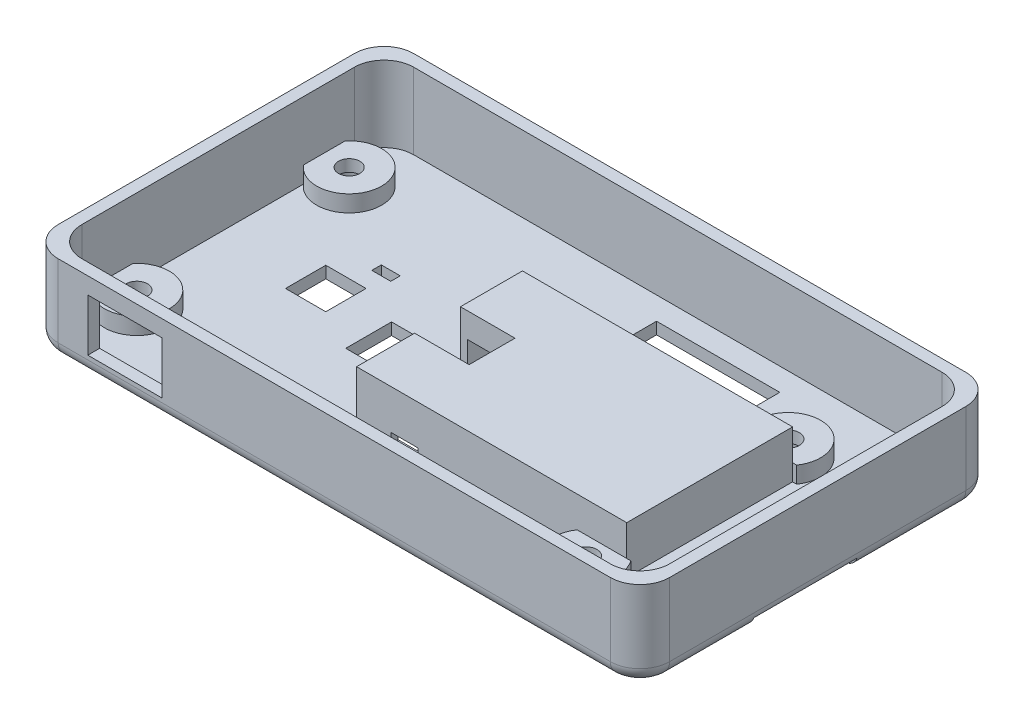
SolidWorks part; units mm, degrees
material "ABS"
ref_plane "Спереди" through (0, 0, 0) normal (0, 0, 1) x (1, 0, 0)
ref_plane "Сверху" through (0, 0, 0) normal (0, 1, 0) x (1, 0, 0)
ref_plane "Справа" through (0, 0, 0) normal (1, 0, 0) x (0, 0, -1)
sketch "Эскиз1" plane through (0, 0, 0) normal (0, 1, 0) x (1, 0, 0)
  line L11 (61.92, -36) -> (-61.92, -36)
  line L12 (61.92, -36) -> (61.92, 36)
  line L13 (61.92, 36) -> (-61.92, 36)
  line L14 (-61.92, -36) -> (-61.92, 36)
  point P0 (0, 0)
extrude "Бобышка-Вытянуть1" add sketch "Эскиз1" along normal blind 17.76
sketch "Эскиз8" plane through (0, 17.76, 0) normal (0, 1, 0) x (1, 0, 0)
  line L7 (-59.52, 33.6) -> (59.52, 33.6)
  line L8 (-59.52, 33.6) -> (-59.52, -33.6)
  line L9 (-59.52, -33.6) -> (59.52, -33.6)
  line L10 (59.52, 33.6) -> (59.52, -33.6)
extrude "Вырез-Вытянуть5" cut sketch "Эскиз8" against normal blind 15.36
sketch "Эскиз10" plane through (0, 2.4, 0) normal (0, 1, 0) x (1, 0, 0)
  line L0 (-61.92, 0) -> (96.256, 0) construction
  line L1 (-61.92, 36) -> (-61.92, -36) construction
  line L3 (42.24, 14.6) -> (42.24, -19)
  line L4 (42.24, -19) -> (-12.48, -19)
  line L5 (-12.48, 14.6) -> (-12.48, -19)
  line L9 (42.24, 14.6) -> (-12.48, 14.6)
sketch "Эскиз11" plane through (0, 0, 33.6) normal (0, 0, 1) x (1, 0, 0)
  line L3 (-49.92, 3.84) -> (-34.92, 3.84)
  line L4 (-49.92, 3.84) -> (-49.92, 14.4)
  line L5 (-49.92, 14.4) -> (-34.92, 14.4)
  line L6 (-34.92, 3.84) -> (-34.92, 14.4)
extrude "Бобышка-Вытянуть2" add sketch "Эскиз10" along normal blind 9.64
extrude "Вырез-Вытянуть7" cut sketch "Эскиз11" along normal blind 5
sketch "Эскиз12" plane through (0, 0, 0) normal (0, -1, 0) x (1, 0, 0)
  line L0 (-59.52, 0) -> (69.6149, 0) construction
  line L2 (40.32, -12.68) -> (40.32, 17.56)
  line L3 (-11.04, 17.56) -> (40.32, 17.56)
  line L4 (-11.04, -12.68) -> (-11.04, 17.56)
  line L9 (-11.04, -12.68) -> (40.32, -12.68)
  point P3 (57.4685, 0)
extrude "Вырез-Вытянуть8" cut sketch "Эскиз12" against normal blind 7
sketch "Эскиз13" plane through (0, 0, 0) normal (0, -1, 0) x (1, 0, 0)
  line L1 (-59.52, 0) -> (-76.8441, 0) construction
  line L8 (37.32, 12.76) -> (61.92, 12.76)
  line L9 (37.32, -8.2) -> (37.32, 12.76)
  line L10 (61.92, -8.2) -> (61.92, 12.76)
  line L11 (61.92, -8.2) -> (37.32, -8.2)
  point P12 (0, 0)
extrude "Вырез-Вытянуть9" cut sketch "Эскиз13" against normal blind 2
sketch "Эскиз21" plane through (0, 7, 0) normal (0, -1, 0) x (1, 0, 0)
  line L1 (0, 0) -> (59.52, 0) construction
  line L8 (-1.44, 7.24) -> (-1.44, -2.04)
  line L9 (-26.44, 7.24) -> (-1.44, 7.24)
  line L10 (-15.8624, -2.04) -> (-1.44, -2.04)
  line L11 (-26.44, -2.04) -> (-26.44, 7.24)
  line L12 (-26.44, -2.04) -> (-15.8624, -2.04)
extrude "Вырез-Вытянуть16" cut sketch "Эскиз21" against normal through all both and the other way through all
sketch "Эскиз14" plane through (0, 0, 0) normal (0, -1, 0) x (1, 0, 0)
  circle A1 centre (-54.48, -21.5) radius 2.16
  circle A3 centre (37.64, -18.3) radius 2.26
  circle A4 centre (37.64, 22.7) radius 2.26
  circle A6 centre (-54.48, 21.5) radius 2.16
  point P4 (0, 0)
sketch "Эскиз22" plane through (0, 0, 0) normal (0, -1, 0) x (1, 0, 0)
  line L0 (-59.52, 0) -> (59.52, 0) construction
  circle A0 centre (37.64, -18.3) radius 3.71
  circle A1 centre (37.64, 22.7) radius 3.71
  circle A4 centre (-54.48, 21.5) radius 3.12
  circle A5 centre (-54.48, -21.5) radius 3.12
fillet "Скругление1" radius 6 4 edges at (-61.92, 8.88, 36) (-61.92, 8.88, -36) (61.92, 8.88, -36) (61.92, 8.88, 36)
fillet "Скругление3" radius 3 8 edges at (60.1626, 0, -34.2426) (0, 0, -36) (-60.1626, 0, -34.2426) (-61.92, 0, 0) (-60.1626, 0, 34.2426) (61.92, 0, 21.38) (60.1626, 0, 34.2426) (0, 0, 36)
fillet "Скругление5" radius 6 4 edges at (-59.52, 10.08, 33.6) (-59.52, 10.08, -33.6) (59.52, 10.08, 33.6) (59.52, 10.08, -33.6) tangent propagation no
sketch "Эскиз19" plane through (0, 0, 17.56) normal (0, 0, -1) x (-1, 0, 0)
  line L4 (5.5, 2) -> (0, 2)
  line L5 (5.5, 2) -> (5.5, 4)
  line L6 (5.5, 4) -> (0, 4)
  line L7 (0, 2) -> (0, 4)
extrude "Вырез-Вытянуть14" cut sketch "Эскиз19" against normal blind 3.84
sketch "Эскиз20" plane through (0, 0, -12.68) normal (0, 0, 1) x (1, 0, 0)
  line L4 (-5.5, 2) -> (0, 2)
  line L5 (-5.5, 2) -> (-5.5, 4)
  line L6 (-5.5, 4) -> (0, 4)
  line L7 (0, 2) -> (0, 4)
extrude "Вырез-Вытянуть15" cut sketch "Эскиз20" against normal blind 3.84
sketch "Эскиз23" plane through (0, 2.4, 0) normal (0, 1, 0) x (1, 0, 0)
  line L1 (-59.52, 25.7302) -> (-59.52, 17.2698)
  line L3 (-59.52, 27.6) -> (-59.52, -27.6) construction
  line L4 (-59.52, -25.7302) -> (-59.52, -17.2698)
  arc A0 (-59.52, 17.2698) -> (-59.52, 25.7302) centre (-54.48, 21.5) ccw
  arc A2 (-59.52, -25.7302) -> (-59.52, -17.2698) centre (-54.48, -21.5) ccw
sketch "Эскиз24" plane through (0, 2.4, 0) normal (0, 1, 0) x (1, 0, 0)
  line L3 (-59.52, 0) -> (71.623, 0) construction
  line L6 (32.1988, -19) -> (43.0812, -19)
  line L7 (32.1988, 14.6) -> (43.0759, 14.5923)
  arc A2 (32.1988, -19) -> (43.0812, -19) centre (37.64, -22.7) ccw
  arc A3 (32.1988, 14.6) -> (43.0759, 14.5923) centre (37.64, 18.3) cw
extrude "Бобышка-Вытянуть3" add sketch "Эскиз24" along normal blind 3.36
extrude "Бобышка-Вытянуть4" add sketch "Эскиз23" along normal blind 3.36
sketch "Эскиз25" plane through (0, 0, 0) normal (0, 1, 0) x (1, 0, 0)
  line L0 (-59.52, 0) -> (57.2984, 0) construction
  circle A0 centre (-54.48, -21.5) radius 2.16
  circle A1 centre (-54.48, 21.5) radius 2.16
  circle A4 centre (37.64, 18.3) radius 2.26
  circle A5 centre (37.64, -22.7) radius 2.26
extrude "Вырез-Вытянуть17" cut sketch "Эскиз25" along normal through all
extrude "Вырез-Вытянуть18" cut sketch "Эскиз22" against normal blind 3.36
sketch "Эскиз26" plane through (0, 0, 0) normal (0, -1, 0) x (1, 0, 0)
  line L0 (-59.52, 0) -> (71.8908, 0) construction
  line L2 (0.2816, -17.96) -> (0.2816, -29)
  line L7 (25.2416, -29) -> (0.2816, -29)
  line L8 (-33.64, -11) -> (-37.48, -11)
  line L9 (-34.88, 2.84) -> (-43.04, 2.84)
  line L10 (-34.88, 2.84) -> (-34.88, -5.32)
  line L11 (-34.88, -5.32) -> (-43.04, -5.32)
  line L12 (-43.04, 2.84) -> (-43.04, -5.32)
  line L13 (-37.48, -11) -> (-37.48, -9.08)
  line L14 (-37.48, -9.08) -> (-33.64, -9.08)
  line L15 (-33.64, -9.08) -> (-33.64, -11)
  line L16 (25.2416, -17.96) -> (25.2416, -29)
  line L17 (25.2416, -17.96) -> (0.2816, -17.96)
extrude "Вырез-Вытянуть19" cut sketch "Эскиз26" against normal through all
